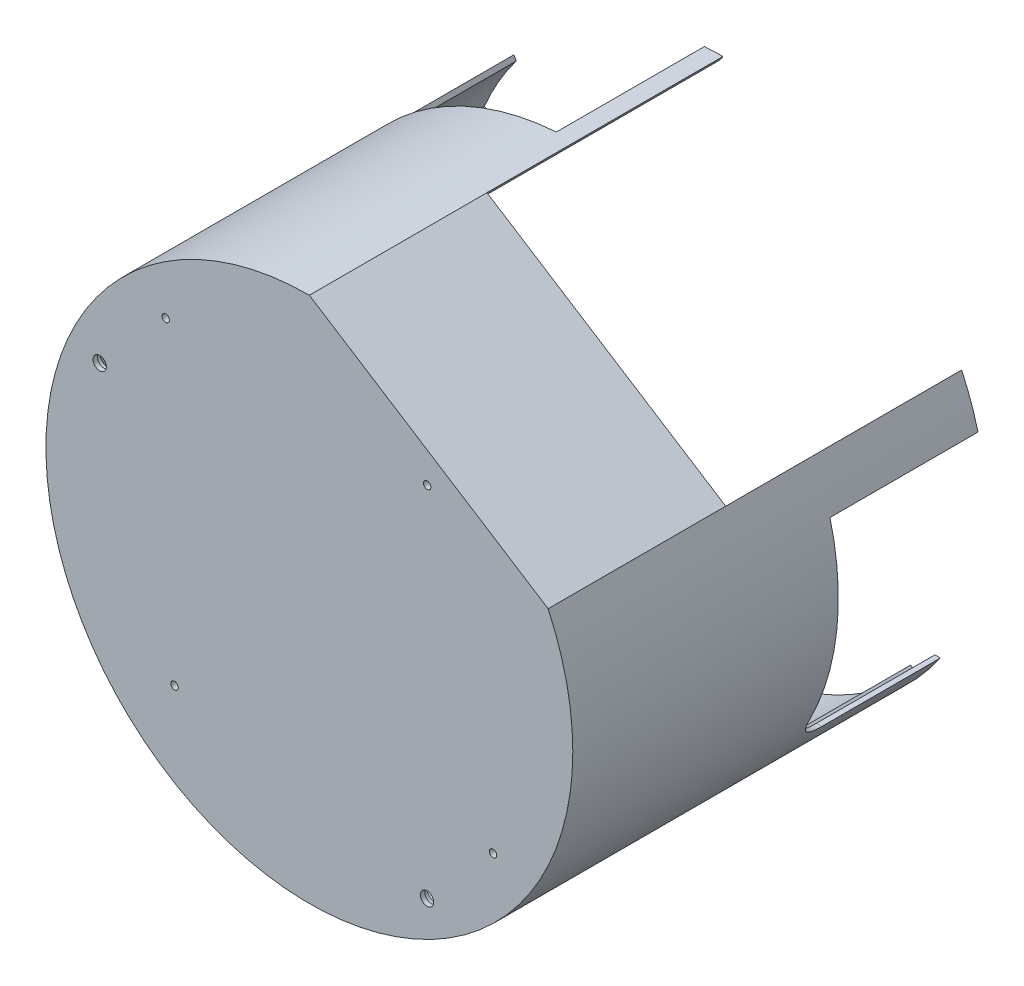
SolidWorks part; units mm, degrees
material "尼龙 101"
ref_plane "前视基准面" through (0, 0, 0) normal (0, 0, 1) x (1, 0, 0)
ref_plane "上视基准面" through (0, 0, 0) normal (0, 1, 0) x (1, 0, 0)
ref_plane "右视基准面" through (0, 0, 0) normal (1, 0, 0) x (0, 0, -1)
sketch "草图1" plane through (0, 0, 0) normal (0, 0, 1) x (1, 0, 0)
  line L0 (0, 0) -> (80.6614, 37.613) construction
  line L1 (0, 89) -> (0, 0) construction
  line L2 (-0.4355, 87.4989) -> (79.485, 36.5839)
  line L3 (80.6614, 37.613) -> (0, 89)
  arc A0 (-0.4355, 87.4989) -> (79.485, 36.5839) centre (0, 0) ccw
  arc A1 (0, 89) -> (80.6614, 37.613) centre (0, 0) ccw
  dimension "D1" = 175
  dimension "D2" = 178
  dimension "D4" = 1.5
  dimension "D3" = 65
extrude "拉伸1" add sketch "草图1" along normal blind 136
sketch "草图2" plane through (40.3307, 63.3065, 0) normal (0.5373, 0.8434, 0) x (0.8434, -0.5373, 0)
  line L0 (47.8197, -136) -> (47.8197, 0) construction
  line L1 (47.8197, -76) -> (-47.8197, -76)
  line L2 (47.8197, -76) -> (47.8197, 0)
  line L3 (47.8197, 0) -> (-47.8197, 0)
  line L4 (-47.8197, -76) -> (-47.8197, 0)
  line L5 (47.8197, -136) -> (-47.8197, -136) construction
  dimension "D1" = 60
extrude "拉伸2" cut sketch "草图2" against normal up to next
ref_plane "基准面1" through (0, 0, 26) normal (0, 0, 1) x (1, 0, 0)
sketch "草图7" plane through (0, 0, 136) normal (0, 0, 1) x (1, 0, 0)
  line L1 (0, 0) -> (65.8064, 65.8064) construction
  line L3 (0, 0) -> (-90.2025, -98.4387) construction
  line L4 (0, 0) -> (8.3865, -87.0972) construction
  arc A1 (-0.4355, 87.4989) -> (79.485, 36.5839) centre (0, 0) ccw construction
  dimension "D1" = 48
sketch "草图10" plane through (0, 0, 136) normal (0, 0, 1) x (1, 0, 0)
  line L0 (0, 0) -> (88.9153, -3.8821) construction
  line L1 (0, 0) -> (-41.0956, 78.944) construction
  line L2 (0, 0) -> (40.3307, 63.3065) construction
  line L3 (80.6614, 37.613) -> (0, 89) construction
  arc A0 (0, 89) -> (80.6614, 37.613) centre (0, 0) ccw construction
  dimension "D1" = 120
  dimension "D2" = 60
ref_plane "基准面7" through (0, 0, 0) normal (-0.8434, 0.5373, 0) x (0, 0, 1)
ref_plane "基准面8" through (-47.8197, -75.0618, 136) normal (-0.5373, -0.8434, 0) x (0.8434, -0.5373, 0)
sketch "草图15" plane through (0, 0, 136) normal (0, 0, 1) x (1, 0, 0)
  line L0 (80.6614, 37.613) -> (0, 89) construction
  line L1 (80.6614, 37.613) -> (0, 89)
  arc A2 (0, 89) -> (80.6614, 37.613) centre (0, 0) ccw construction
  arc A3 (0, 89) -> (80.6614, 37.613) centre (0, 0) ccw
extrude "拉伸11" add sketch "草图15" against normal blind 3
sketch "Sketch3" plane through (-47.8197, -75.0618, 136) normal (-0.5373, -0.8434, 0) x (0.8434, -0.5373, 0)
  line L0 (45, -30) -> (45, -55) construction
  line L1 (55, -30) -> (55, -55)
  line L2 (35, -30) -> (35, -55)
  line L3 (89, 0) -> (-89, 0) construction
  arc A0 (55, -30) -> (35, -30) centre (45, -30) ccw
  arc A1 (35, -55) -> (55, -55) centre (45, -55) ccw
  point P2 (45, -42.5)
  point P9 (0, 0)
  dimension "D2" = 10
  dimension "D1" = 45
  dimension "D3" = 25
  dimension "D4" = 30
extrude "Extrude5" cut sketch "Sketch3" against normal up to next
mirror "Mirror2" about plane through (0, 0, 0) normal (-0.8434, 0.5373, 0) of "Extrude5"
sketch "草图16" plane through (0, 0, 136) normal (0, 0, 1) x (1, 0, 0)
  line L0 (0, 0) -> (51.1074, 55.774) construction
  line L1 (0, 0) -> (-80.0434, 73.3463) construction
  line L2 (0, 0) -> (108.7277, -69.2672) construction
  line L3 (0, 0) -> (-76.4646, 99.6507) construction
  line L4 (0, 0) -> (-111.3102, -57.9444) construction
  line L5 (0, 0) -> (-42.7518, -103.2119) construction
  circle A0 centre (0, 0) radius 60 construction
  circle A1 centre (0, 0) radius 25 construction
  circle A2 centre (-36.5257, 47.6012) radius 27.5 construction
  circle A3 centre (50.6035, -32.238) radius 27.5 construction
  arc A4 (-50.4586, -55.0659) -> (-25.7231, -28.0718) centre (-22.961, -55.4328) ccw construction
  arc A5 (-25.7231, -28.0718) -> (-50.4586, -55.0659) centre (-53.2206, -27.7049) ccw construction
  circle A6 centre (39.7572, -67.6266) radius 2.25
  circle A7 centre (-70.8344, 33.7119) radius 2.25
  dimension "D5" = 120
  dimension "D6" = 50
  dimension "D7" = 55
  dimension "D8" = 55
  dimension "D9" = 55
  dimension "D10" = 55
  dimension "D11" = 23
  dimension "D12" = 23
  dimension "D13" = 4.5
  dimension "D15" = 150
  dimension "D16" = 75
  dimension "D1" = 10
  dimension "D2" = 10
  dimension "D3" = 20
  dimension "D4" = 20
extrude "拉伸12" cut sketch "草图16" against normal blind 1.5
sketch "草图17" plane through (0, 0, 134.5) normal (0, 0, 1) x (1, 0, 0)
  line L0 (-70.8344, 33.7119) -> (39.7572, -67.6266) construction
  circle A0 centre (-70.8344, 33.7119) radius 3
  circle A1 centre (39.7572, -67.6266) radius 3
extrude "拉伸13" cut sketch "草图17" against normal blind 2
sketch "草图18" plane through (-47.8197, -75.0618, 136) normal (-0.5373, -0.8434, 0) x (0.8434, -0.5373, 0)
  line L0 (89, 0) -> (-89, 0) construction
  line L1 (-37.7889, -115) -> (-37.7889, -140) construction
  line L3 (-81.7889, -140) -> (-81.7889, -115) construction
  line L4 (-81.7889, -115) -> (-37.7889, -115) construction
  line L5 (-81.7889, -115) -> (-81.7889, -140)
  line L6 (-81.7889, -140) -> (-37.7889, -140)
  line L7 (-37.7889, -140) -> (-37.7889, -115)
  arc A0 (-78.2644, -93.0682) -> (-81.7889, -115) centre (-11.7889, -115) ccw
  arc A1 (-37.7889, -115) -> (-54.9034, -84.915) centre (-72.7889, -115) ccw
  arc A3 (-54.9034, -84.915) -> (-78.2644, -93.0682) centre (-63.7889, -97) ccw
  spline S1 degree 3 poles (-81.7889, -115) (-81.7889, -112.8074) (-81.7083, -110.6558) (-81.4664, -107.486) (-81.3654, -106.4391) (-81.1806, -104.8835) (-81.1133, -104.3661) (-80.9685, -103.3467) (-80.891, -102.8439) (-80.477, -100.3628) (-80.063, -98.4831) (-79.2946, -95.8148) (-79.0122, -94.9472) (-78.4032, -93.2949) (-78.0761, -92.5069) (-77.3729, -91.0051) (-76.9969, -90.2912) (-76.1909, -88.9374) (-75.7603, -88.2967) (-74.3819, -86.4947) (-73.3732, -85.4847) (-71.7075, -84.2481) (-71.1267, -83.8827) (-69.9097, -83.2485) (-69.2703, -82.9793) (-67.3088, -82.3385) (-65.9319, -82.124) (-64.121, -82.1209) (-63.7543, -82.1337) (-63.0117, -82.1864) (-62.6347, -82.2265) (-61.4992, -82.3873) (-60.7377, -82.5477) (-58.4418, -83.1825) (-56.8957, -83.809) (-54.565, -85.0591) (-53.7957, -85.523) (-52.2842, -86.5361) (-51.5403, -87.0861) (-50.0788, -88.2723) (-49.3611, -88.9085) (-48.3073, -89.9288) (-47.9589, -90.2809) (-47.2757, -91.0019) (-46.9409, -91.3707) (-45.3005, -93.256) (-44.096, -94.8948) (-42.7443, -97.111) (-42.4817, -97.5628) (-41.9729, -98.4836) (-41.7261, -98.9539) (-41.0187, -100.3772) (-40.5891, -101.3453) (-39.4292, -104.3069) (-38.8265, -106.3573) (-38.3112, -109.0224) (-38.22, -109.5618) (-38.0637, -110.6422) (-37.9985, -111.1838) (-37.8417, -112.8125) (-37.7889, -113.9035) (-37.7889, -115) knots 0 0 0 0 0.0625 0.0625 0.09375 0.09375 0.109375 0.109375 0.125 0.125 0.1875 0.1875 0.21875 0.21875 0.25 0.25 0.28125 0.28125 0.3125 0.3125 0.375 0.375 0.40625 0.40625 0.4375 0.4375 0.5 0.5 0.515625 0.515625 0.53125 0.53125 0.5625 0.5625 0.625 0.625 0.65625 0.65625 0.6875 0.6875 0.71875 0.71875 0.734375 0.734375 0.75 0.75 0.8125 0.8125 0.828125 0.828125 0.84375 0.84375 0.875 0.875 0.9375 0.9375 0.953125 0.953125 0.96875 0.96875 1 1 1 1 construction
  point P7 (0, 0)
  dimension "D1" = 70
  dimension "D2" = 140
  dimension "D3" = 30
  dimension "D4" = 44
  dimension "D8" = 43
  dimension "D9" = 18
  dimension "D5" = 38
  dimension "D6" = 25
  dimension "D7" = 140
extrude "拉伸19" [suppressed] cut sketch "草图18" against normal up to surface (20.7278 mm away)
mirror "镜向4" [suppressed] about plane through (0, 0, 0) normal (-0.8434, 0.5373, 0)
ref_plane "基准面10" through (40.3307, -25.6935, 0) normal (0.8434, -0.5373, 0) x (0, 0, -1)
sketch "草图22" plane through (40.3307, -25.6935, 0) normal (0.8434, -0.5373, 0) x (0, 0, -1)
  line L0 (-136, 75.0618) -> (-76, 75.0618) construction
  line L1 (-23, 17.0618) -> (5, 17.0618)
  line L3 (-55, 49.0618) -> (-55, 75.0618)
  line L4 (-55, 75.0618) -> (5, 75.0618)
  line L5 (5, 75.0618) -> (5, 17.0618)
  arc A0 (-55, 49.0618) -> (-23, 17.0618) centre (-23, 49.0618) ccw
  dimension "D1" = 26
  dimension "D6" = 141
  dimension "D4" = 58
  dimension "D5" = 60
extrude "拉伸22" cut sketch "草图22" along normal blind 52 and the other way blind 10 contours L5 L1 A0 L3 L4
mirror "镜向6" about plane through (0, 0, 0) normal (-0.8434, 0.5373, 0) of "拉伸22"
sketch "草图28" plane through (0, 0, 133) normal (0, 0, -1) x (-1, 0, 0)
  line L0 (-37.838, 63.116) -> (-41.2115, 60.9668)
  line L1 (-79.485, 36.5839) -> (0.4355, 87.4989) construction
  line L2 (-41.2115, 60.9668) -> (-40.1369, 59.28)
  line L3 (-40.1369, 59.28) -> (-36.7634, 61.4292)
  line L4 (-36.7634, 61.4292) -> (-37.838, 63.116)
  point P4 (-39.5247, 62.0414)
  dimension "D1" = 4
  dimension "D2" = 2
  dimension "D3" = 2
extrude "拉伸25" add sketch "草图28" along normal up to surface (57 mm away) up to face at (39.7425, 62.3832, 76)
sketch "草图29" plane through (0, 0, 133) normal (0, 0, -1) x (-1, 0, 0)
  line L0 (0, 0) -> (65.3967, -58.8835) construction
  line L1 (0, 0) -> (78.057, -40.6339) construction
  line L2 (61.8116, -58.3466) -> (64.4881, -55.3741) construction
  line L3 (64.4881, -55.3741) -> (66.7641, -57.3284) construction
  line L4 (61.8116, -58.3466) -> (63.9931, -60.4059) construction
  line L5 (75.3388, -41.4737) -> (77.1858, -37.9256)
  line L6 (77.1858, -37.9256) -> (78.9808, -38.8076)
  line L7 (75.3388, -41.4737) -> (77.0909, -42.4382)
  arc A0 (77.0909, -42.4382) -> (78.9808, -38.8076) centre (0, 0) ccw
  arc A1 (63.9931, -60.4059) -> (66.7641, -57.3284) centre (0, 0) ccw construction
  point P6 (0, 0)
  point P8 (63.1498, -56.8604)
  point P13 (76.2623, -39.6996)
  dimension "D4" = 2
  dimension "D6" = 4
  dimension "D1" = 176
  dimension "D2" = 14.5
  dimension "D3" = 4
  dimension "D5" = 3
extrude "拉伸26" add sketch "草图29" along normal up to surface (133 mm away) up to face at (-19.1247, -30.0197, 0)
sketch "草图34" plane through (0, 0, 133) normal (0, 0, -1) x (-1, 0, 0)
  line L0 (-62.1569, -61.5855) -> (-60.7043, -60.2107)
  line L1 (-60.7043, -60.2107) -> (-63.454, -57.3056)
  line L2 (-63.454, -57.3056) -> (-64.9065, -58.6804)
  arc A0 (-79.485, 36.5839) -> (76.6529, -42.197) centre (0, 0) ccw construction
  arc A1 (-64.9065, -58.6804) -> (-62.1569, -61.5855) centre (0, 0) ccw
  dimension "D3" = 2
  dimension "D1" = 2
  dimension "D2" = 4
extrude "拉伸27" add sketch "草图34" along normal up to surface (133 mm away) up to face at (-42.5367, -30.0017, 0)
ref_axis "基准轴2" through (0, 0, 97.9) along (0, 0, -1)
sketch "草图39" plane through (0, 0, 136) normal (0, 0, 1) x (1, 0, 0)
  line L0 (0, 0) -> (40.3307, 63.3065)
  line L1 (80.6614, 37.613) -> (0, 89)
  line L2 (80.6614, 37.613) -> (0, 89)
  line L3 (0, 89) -> (80.6614, 37.613) construction
  arc A1 (0, 89) -> (80.6614, 37.613) centre (0, 0) ccw
  arc A2 (0, 89) -> (80.6614, 37.613) centre (0, 0) ccw
  dimension "D1" = 0
ref_plane "基准面12" through (0, 0, 0) normal (0.8434, -0.5373, 0) x (0, 0, -1)
mirror "镜向9" about plane through (0, 0, 0) normal (0.8434, -0.5373, 0) of "拉伸26"
mirror "镜向8" about plane through (0, 0, 0) normal (-0.8434, 0.5373, 0) of "拉伸27"
sketch "Sketch4" plane through (-47.8197, -75.0618, 136) normal (-0.5373, -0.8434, 0) x (0.8434, -0.5373, 0)
  line L0 (89, 0) -> (-89, 0) construction
  line L1 (-35.5, -10) -> (35.5, -10)
  line L2 (-37.5, -12) -> (-37.5, -23)
  line L3 (-35.5, -25) -> (35.5, -25)
  line L4 (37.5, -12) -> (37.5, -23)
  arc A0 (-37.5, -12) -> (-35.5, -10) centre (-35.5, -12) cw
  arc A1 (35.5, -10) -> (37.5, -12) centre (35.5, -12) cw
  arc A2 (37.5, -23) -> (35.5, -25) centre (35.5, -23) cw
  arc A3 (-37.5, -23) -> (-35.5, -25) centre (-35.5, -23) ccw
  point P4 (0, -10)
  point P7 (0, 0)
  point P14 (37.5, -25)
  point P17 (-37.5, -25)
  dimension "D4" = 2
  dimension "D1" = 25
  dimension "D2" = 15
  dimension "D3" = 75
extrude "Extrude6" [suppressed] cut sketch "Sketch4" against normal up to next
sketch "Sketch2" plane through (0, 0, 0) normal (0, 1, 0) x (1, 0, 0)
  line L0 (0, -23) -> (32, -23) construction
  line L1 (32, -23) -> (32, 9)
  line L2 (32, 9) -> (0, 9)
  arc A0 (0, 9) -> (32, -23) centre (0, -23) ccw
  dimension "D1" = 64
  dimension "D2" = 23
sketch "Sketch1" plane through (0, 0, 0) normal (0, 0, -1) x (-1, 0, 0)
  line L0 (60.4653, -65.9863) -> (40.1976, -43.868) construction
  line L1 (89.4905, 1.3006) -> (-9.0953, -89.0367)
  arc A0 (-9.0953, -89.0367) -> (89.4905, 1.3006) centre (0, 0) ccw
  dimension "D1" = 30
extrude "Extrude3" cut sketch "Sketch1" against normal blind 20
draft "拔模1" [suppressed] type of draft neutral plane draft angle 0.5 faces to draft 2 reverse direction yes parameters "D1"=0.5
draft "拔模2" [suppressed] type of draft neutral plane draft angle 0.5 faces to draft 22 parameters "D1"=0.5
sketch "草图35" plane through (0, 0, 136) normal (0, 0, 1) x (1, 0, 0)
  line L0 (-29.0165, 36.3442) -> (45.2019, -10.9382)
  line L1 (80.6614, 37.613) -> (0, 89) construction
  line L2 (0, 0) -> (8.0927, 12.703) construction
  line L3 (-45.1355, 11.0425) -> (29.083, -36.2399)
  line L4 (0, 0) -> (-8.0263, -12.5987) construction
  line L5 (-70.8344, 33.7119) -> (39.7572, -67.6266) construction
  point P14 (-24.1453, -37.9005)
  dimension "D1" = 88
  dimension "D2" = 60
  dimension "D3" = 88
  dimension "D4" = 30
  dimension "D5" = 1.3823
  dimension "D6" = 120
sketch "草图37" plane through (0, 0, 136) normal (0, 0, 1) x (1, 0, 0)
  line L0 (80.6614, 37.613) -> (0, 89) construction
  line L1 (62.0517, -43.2965) -> (-48.5399, 58.042) construction
  line L2 (0, 0) -> (6.7559, 7.3728) construction
  line L4 (40.3307, 63.3065) -> (39.7881, 53.3212) construction
  circle A0 centre (62.0517, -43.2965) radius 3
  circle A1 centre (-48.5399, 58.042) radius 3
  circle A4 centre (-45.5401, -47.9842) radius 3
  circle A5 centre (39.7881, 53.3212) radius 3
  dimension "D1" = 10
  dimension "D2" = 140
  dimension "D3" = 6
  dimension "D4" = 10
  dimension "D5" = 150
extrude "拉伸28" add sketch "草图37" against normal blind 6
chamfer "倒角1" distance 3 angle 10 4 edges at (-42.5401, -47.9842, 130) (42.7881, 53.3212, 130) (-45.5399, 58.042, 130) (65.0517, -43.2965, 130) first distance on face at (-42.5401, -47.9842, 130) first distance on face at (42.7881, 53.3212, 130) first distance on face at (-45.5399, 58.042, 130) first distance on face at (65.0517, -43.2965, 130)
sketch "草图40" plane through (0, 0, 136) normal (0, 0, 1) x (1, 0, 0)
  line L0 (0, 0) -> (40.3307, 63.3065)
  line L1 (80.6614, 37.613) -> (0, 89) construction
  line L3 (0, 0) -> (38.8054, 38.8054)
  line L4 (0, 0) -> (80.6614, 37.613)
sketch "草图41" plane through (0, 0, 133) normal (0, 0, -1) x (-1, 0, 0)
  line L4 (-1.9629, -44.9572) -> (1.9629, 44.9572)
ref_plane "基准面13" through (0, 0, 0) normal (0.9763, 0.2164, 0) x (0, 0, -1)
sketch "草图42" plane through (0, 0, 0) normal (0.9763, 0.2164, 0) x (0, 0, -1)
  line L0 (0, -1.5) -> (-23, -1.5) construction
  line L1 (-23, -34.5) -> (10, -34.5)
  line L3 (-23, 31.5) -> (10, 31.5)
  line L4 (10, 31.5) -> (10, -1.5)
  line L5 (10, -34.5) -> (10, -1.5)
  arc A0 (-23, 31.5) -> (-23, -34.5) centre (-23, -1.5) ccw
  dimension "D2" = 33
  dimension "D1" = 23
  dimension "D3" = 1.5
extrude "切除-拉伸1" cut sketch "草图42" against normal blind 100
mirror "镜向10" about plane through (0, 0, 0) normal (0.8434, -0.5373, 0) of "切除-拉伸1"
hole_wizard "M3 螺纹孔1" positions "3D草图2" profile "草图45" tap size "M3" standard "GB" end condition through all
sketch3d "3D草图2"
  point P0 (-48.5399, 58.042, 136)
  point P3 (62.0517, -43.2965, 136)
  point P6 (-45.5401, -47.9842, 136)
  point P9 (39.7881, 53.3212, 136)
sketch "草图45" plane through (-48.5399, 58.042, 136) normal (1, 0, 0) x (0, -1, 0)
  line L0 (0, 0) -> (0, 136)
  line L1 (0, 136) -> (1.25, 136)
  line L2 (1.25, 136) -> (1.25, 0)
  line L5 (1.25, 0) -> (0, 0)
  line L11 (0, -6.35) -> (0, 107.95) construction
  dimension "通孔螺纹孔钻头直径" = 2.5
  dimension "通孔螺纹孔钻头深度" = 136
cosmetic thread "Hole Thread1" parameters "D1"=6, "D2"=3.5
cosmetic thread "Hole Thread2" parameters "D1"=6, "D2"=3.5
cosmetic thread "Hole Thread3" parameters "D1"=6, "D2"=3.5
cosmetic thread "Hole Thread4" parameters "D1"=6, "D2"=3.5
sketch "Sketch5" plane through (40.3307, 63.3065, 0) normal (0.5373, 0.8434, 0) x (0.8434, -0.5373, 0)
  line L1 (-101.7424, 25.2211) -> (107.7902, 25.2211)
  line L2 (-101.7424, 25.2211) -> (-101.7424, -56.2996)
  line L3 (-101.7424, -56.2996) -> (107.7902, -56.2996)
  line L4 (107.7902, 25.2211) -> (107.7902, -56.2996)
extrude "Cut-Extrude1" cut sketch "Sketch5" against normal blind 342
sketch "Sketch7" plane through (0, 0, 56.2996) normal (0, 0, -1) x (-1, 0, 0)
  line L14 (-63.454, -57.3056) -> (-64.9065, -58.6804)
  line L15 (-79.7024, 36.1078) -> (-80.6614, 37.613)
  line L16 (0, 89) -> (0.959, 87.4947)
  line L17 (80.6132, 34.0259) -> (78.7533, 33.2905)
  line L18 (78.7533, 33.2905) -> (80.2242, 29.5707)
  line L19 (80.2242, 29.5707) -> (82.084, 30.3061)
  line L20 (78.5321, -38.5871) -> (77.1858, -37.9256)
  line L21 (77.1858, -37.9256) -> (75.3388, -41.4737)
  line L22 (75.3388, -41.4737) -> (76.6529, -42.197)
  line L23 (5.8486, -87.3043) -> (5.7483, -85.8077)
  line L24 (5.7483, -85.8077) -> (1.7522, -85.9821)
  line L25 (1.7522, -85.9821) -> (1.7827, -87.4818)
  line L26 (-62.1569, -61.5855) -> (-60.7043, -60.2107)
  line L27 (-60.7043, -60.2107) -> (-63.454, -57.3056)
  line L28 (-63.454, -57.3056) -> (-64.9065, -58.6804)
  line L29 (-79.7024, 36.1078) -> (-80.6614, 37.613)
  line L30 (0, 89) -> (0.959, 87.4947)
  line L31 (80.6132, 34.0259) -> (78.7533, 33.2905)
  line L32 (78.7533, 33.2905) -> (80.2242, 29.5707)
  line L33 (80.2242, 29.5707) -> (82.084, 30.3061)
  line L34 (78.5321, -38.5871) -> (77.1858, -37.9256)
  line L35 (77.1858, -37.9256) -> (75.3388, -41.4737)
  line L36 (75.3388, -41.4737) -> (76.6529, -42.197)
  line L37 (5.8486, -87.3043) -> (5.7483, -85.8077)
  line L38 (5.7483, -85.8077) -> (1.7522, -85.9821)
  line L39 (1.7522, -85.9821) -> (1.7827, -87.4818)
  line L40 (-62.1569, -61.5855) -> (-60.7043, -60.2107)
  line L41 (-60.7043, -60.2107) -> (-63.454, -57.3056)
  arc A6 (-79.7024, 36.1078) -> (-64.9065, -58.6804) centre (0, 0) ccw
  arc A7 (-80.6614, 37.613) -> (0, 89) centre (0, 0) ccw
  arc A8 (80.6132, 34.0259) -> (0.959, 87.4947) centre (0, 0) ccw
  arc A9 (78.5321, -38.5871) -> (82.084, 30.3061) centre (0, 0) ccw
  arc A10 (5.8486, -87.3043) -> (76.6529, -42.197) centre (0, 0) ccw
  arc A11 (-62.1569, -61.5855) -> (1.7827, -87.4818) centre (0, 0) ccw
  arc A12 (-79.7024, 36.1078) -> (-64.9065, -58.6804) centre (0, 0) ccw
  arc A13 (-80.6614, 37.613) -> (0, 89) centre (0, 0) ccw
  arc A14 (80.6132, 34.0259) -> (0.959, 87.4947) centre (0, 0) ccw
  arc A15 (78.5321, -38.5871) -> (82.084, 30.3061) centre (0, 0) ccw
  arc A16 (5.8486, -87.3043) -> (76.6529, -42.197) centre (0, 0) ccw
  arc A17 (-62.1569, -61.5855) -> (1.7827, -87.4818) centre (0, 0) ccw
  dimension "D1" = 0
extrude "Boss-Extrude1" add sketch "Sketch7" along normal blind 60
sketch "Sketch8" plane through (0, 0, -3.7004) normal (0, 0, -1) x (-1, 0, 0)
  line L13 (0.4355, 87.4989) -> (-37.838, 63.116) construction
  arc A0 (-80.6614, 37.613) -> (0, 89) centre (0, 0) ccw construction
  line B0 (9.3149, 77.4499) -> (12.0612, 82.7256)
  line B1 (-8.0613, 84.21) -> (1.9659, 68.4704)
  line B2 (0.4354, 61.567) -> (-55.9827, 25.6247)
  line B3 (-62.8861, 27.1552) -> (-72.9134, 42.8948)
  line B4 (-80.0722, 24.0302) -> (-74.1301, 24.2896)
  line B5 (-69.9594, 20.4679) -> (-67.6476, -32.4817)
  line B6 (-69.5584, -34.567) -> (-78.8412, -34.9723)
  line B7 (16.5738, -84.6422) -> (11.5814, -76.8057)
  line B8 (12.1936, -74.0443) -> (61.9537, -42.3437)
  line B9 (64.7151, -42.9559) -> (69.7075, -50.7924)
  line B10 (65.0154, 56.6745) -> (60.725, 48.4327)
  line B11 (58.0275, 47.5822) -> (11.0159, 72.0548)
  circle B12 centre (6.5906, 83.7411) radius 1.6
  circle B13 centre (-0.733, 83.9968) radius 1.6
  circle B14 centre (-78.6805, 29.4174) radius 1.6
  circle B15 centre (-75.8172, 36.1629) radius 1.6
  arc B16 (12.0612, 82.7256) -> (8.9138, 88.5525) centre (8.5132, 84.5726) ccw
  arc B17 (8.9138, 88.5525) -> (-5.7241, 88.8157) centre (0, 0) ccw
  arc B18 (-5.7241, 88.8157) -> (-8.0613, 84.21) centre (-5.5312, 85.8219) ccw
  arc B19 (0.4354, 61.567) -> (1.9659, 68.4704) centre (-2.2511, 65.7839) ccw
  arc B20 (-62.8861, 27.1552) -> (-55.9827, 25.6247) centre (-58.6692, 29.8416) ccw
  arc B21 (-72.9134, 42.8948) -> (-78.0753, 42.723) centre (-75.4435, 41.2829) ccw
  arc B22 (-78.0753, 42.723) -> (-84.0229, 29.3453) centre (0, 0) ccw
  arc B23 (-84.0229, 29.3453) -> (-80.0722, 24.0302) centre (-80.2466, 28.0264) ccw
  arc B24 (-69.9594, 20.4679) -> (-74.1301, 24.2896) centre (-73.9556, 20.2934) ccw
  arc B25 (-69.5584, -34.567) -> (-67.6476, -32.4817) centre (-69.6457, -32.5689) ccw
  arc B26 (-78.8412, -34.9723) -> (-80.5644, -37.8203) centre (-78.754, -36.9704) ccw
  arc B27 (-80.5644, -37.8203) -> (15.2293, -87.6873) centre (0, 0) ccw
  arc B28 (15.2293, -87.6873) -> (16.5738, -84.6422) centre (14.8871, -85.7168) ccw
  arc B29 (12.1936, -74.0443) -> (11.5814, -76.8057) centre (13.2682, -75.7311) ccw
  arc B30 (64.7151, -42.9559) -> (61.9537, -42.3437) centre (63.0283, -44.0305) ccw
  arc B31 (69.7075, -50.7924) -> (73.0355, -50.8607) centre (71.3943, -49.7178) ccw
  arc B32 (73.0355, -50.8607) -> (68.3248, 57.0326) centre (0, 0) ccw
  arc B33 (68.3248, 57.0326) -> (65.0154, 56.6745) centre (66.7894, 55.751) ccw
  arc B34 (58.0275, 47.5822) -> (60.725, 48.4327) centre (58.951, 49.3562) ccw
  arc B35 (9.3149, 77.4499) -> (11.0159, 72.0548) centre (12.8629, 75.6029) ccw
sketch_block_instance "Block1-1"
sketch_block "Block1"
sketch "Sketch9" plane through (0, 0, -3.7004) normal (0, 0, -1) x (-1, 0, 0)
  line L0 (10.5068, -75.1189) -> (26.0109, -99.4554) construction
  line L1 (10.5068, -75.1189) -> (63.6405, -41.2691) construction
  line L2 (26.0109, -99.4554) -> (79.1445, -65.6055) construction
  line L3 (63.6405, -41.2691) -> (79.1445, -65.6055) construction
  line L4 (10.5068, -75.1189) -> (79.1445, -65.6055) construction
  line L5 (26.0109, -99.4554) -> (63.6405, -41.2691) construction
  line L6 (12.1936, -74.0443) -> (61.9537, -42.3437) construction
  line L7 (16.5738, -84.6422) -> (11.5814, -76.8057) construction
  line L8 (64.7151, -42.9559) -> (69.7075, -50.7924) construction
  line L17 (65.171, -34.3656) -> (86.048, -67.136)
  line L18 (24.4804, -106.3589) -> (86.048, -67.136)
  line L19 (3.6034, -73.5885) -> (24.4804, -106.3589)
  line L20 (3.6034, -73.5885) -> (65.171, -34.3656)
  line L21 (-57.7671, 23.4436) -> (-96.5856, 21.7487)
  line L22 (-96.5856, 21.7487) -> (-93.4014, -51.1818)
  line L23 (-54.5829, -49.4869) -> (-93.4014, -51.1818)
  line L24 (-57.7671, 23.4436) -> (-54.5829, -49.4869)
  line L25 (56.9504, 28.076) -> (74.8918, 62.5412)
  line L26 (74.8918, 62.5412) -> (10.14, 96.2488)
  line L27 (-7.8014, 61.7836) -> (10.14, 96.2488)
  line L28 (56.9504, 28.076) -> (-7.8014, 61.7836)
  point P1 (44.8257, -70.3622)
  point P9 (24.4804, -106.3589)
  point P22 (0, 0)
  point P28 (0.9289, -7.3563)
  dimension "D1" = 5
  dimension "D2" = 3
extrude "Cut-Extrude2" cut sketch "Sketch9" against normal blind 50
fillet "Fillet1" radius 10 4 edges at (72.5308, -50.2706, 46.2996) (-70.1845, 53.4984, 46.2996) (-12.3868, -87.3757, 46.2996) (-73.9544, -48.1528, 46.2996)
